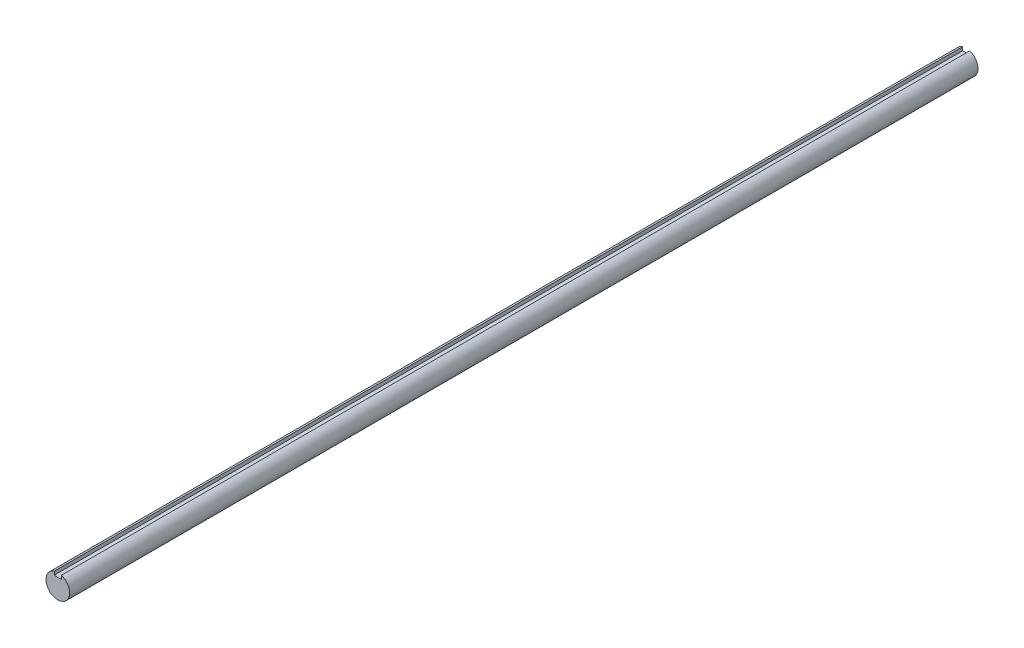
SolidWorks part; units mm, degrees
ref_plane "Front Plane" through (0, 0, 0) normal (0, 0, 1) x (1, 0, 0)
ref_plane "Top Plane" through (0, 0, 0) normal (0, 1, 0) x (1, 0, 0)
ref_plane "Right Plane" through (0, 0, 0) normal (1, 0, 0) x (0, 0, -1)
sketch "Sketch1" plane through (0, 0, 0) normal (1, 0, 0) x (0, 0, -1)
  line L0 (0, 0) -> (0, 3.9687) construction
  line L1 (-228.6, 3.9687) -> (228.6, 3.9687)
  line L2 (-228.6, 3.9687) -> (-228.6, -3.9688)
  line L3 (-228.6, -3.9688) -> (228.6, -3.9688)
  line L4 (228.6, 3.9687) -> (228.6, -3.9688)
  line L5 (-228.6, 3.9687) -> (228.6, -3.9688) construction
  line L6 (-228.6, -3.9688) -> (228.6, 3.9687) construction
  line L7 (0, 0) -> (0, -3.9688) construction
  point P0 (0, 0)
  point P8 (-219.4719, 3.9687)
  point P10 (219.4719, 3.9687)
  point P11 (-216.4292, -3.9688)
  point P12 (218.0598, -3.9688)
  dimension "Diameter" = 7.9375
  dimension "Length" = 457.2
  dimension "D1" = 9.1281
  dimension "D2" = 9.1281
  dimension "D3" = 12.1708
  dimension "D4" = 10.5402
sketch "Sketch2" plane through (0, 0, 0) normal (0, 0, 1) x (1, 0, 0)
  line L0 (0, 0) -> (0, 3.9687) construction
  line L2 (1.1938, 2.5911) -> (-1.1938, 2.5911)
  line L3 (1.1938, 2.5911) -> (1.1938, 3.7849)
  line L4 (1.1938, 3.7849) -> (-1.1938, 3.7849)
  line L5 (-1.1938, 2.5911) -> (-1.1938, 3.7849)
  line L6 (1.1938, 2.5911) -> (-1.1938, 3.7849) construction
  line L7 (1.1938, 3.7849) -> (-1.1938, 2.5911) construction
  circle A0 centre (0, 0) radius 3.9687
  point P3 (0, 3.188)
  dimension "Keyway Width" = 2.3876
  dimension "Keyway Depth" = 1.1938
sketch "Sketch3" plane through (0, 0, 0) normal (0, 0, 1) x (1, 0, 0)
  line L1 (-1.1938, 2.5911) -> (-1.1938, 3.7849) construction
  line L2 (1.1938, 2.5911) -> (-1.1938, 2.5911) construction
  line L3 (1.1938, 2.5911) -> (1.1938, 3.7849) construction
  line L5 (-1.1938, 2.5911) -> (-1.1938, 3.7849)
  line L6 (1.1938, 2.5911) -> (-1.1938, 2.5911)
  line L7 (1.1938, 2.5911) -> (1.1938, 3.7849)
  circle A0 centre (0, 0) radius 3.9687 construction
  arc A1 (-1.1938, 3.7849) -> (1.1938, 3.7849) centre (0, 0) ccw
extrude "Boss-Extrude1" add sketch "Sketch3" along normal blind 152.4 and the other way blind 152.4
equation "\"D2@Sketch1\"=1.15*\"Diameter@Sketch1\""
equation "\"D1@Sketch1\"=\"D2@Sketch1\""
equation "\"D3@Sketch1\"=\"D2@Sketch1\"*4/3"
equation "\"D4@Sketch1\"=\"D2@Sketch1\"/(tan(.5236*180/pi)*2)*4/3"
